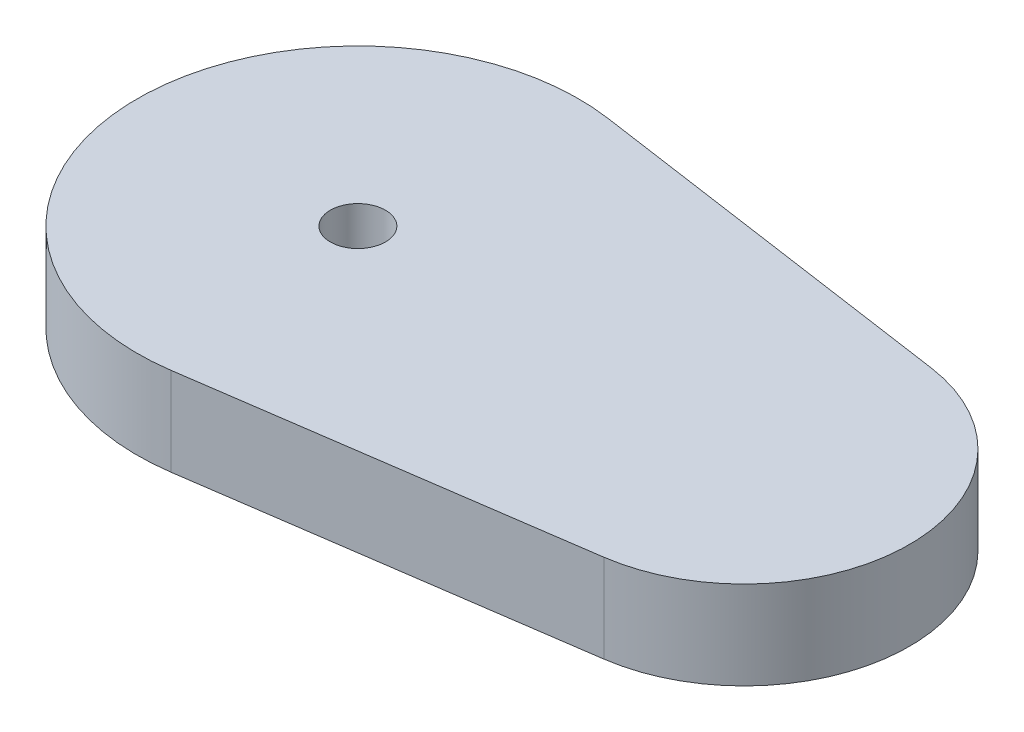
SolidWorks part; units mm, degrees
ref_plane "Front Plane" through (0, 0, 0) normal (0, 0, 1) x (1, 0, 0)
ref_plane "Top Plane" through (0, 0, 0) normal (0, 1, 0) x (1, 0, 0)
ref_plane "Right Plane" through (0, 0, 0) normal (1, 0, 0) x (0, 0, -1)
sketch "Sketch1" plane through (0, 0, 0) normal (0, 1, 0) x (1, 0, 0)
  line L0 (0, 0) -> (14, 0) construction
  line L6 (1.1429, -7.9179) -> (14.8571, -5.9385)
  line L8 (1.1429, 7.9179) -> (14.8571, 5.9385)
  line L11 (14, 0) -> (20, 0) construction
  circle A0 centre (0, 0) radius 1
  arc A1 (1.1429, 7.9179) -> (1.1429, -7.9179) centre (0, 0) ccw
  arc A2 (14.8571, 5.9385) -> (14.8571, -5.9385) centre (14, 0) cw
  point P3 (0, 0)
  dimension "D1" = 2
  dimension "D2" = 20
  dimension "D5" = 8
  dimension "D6" = 6
  dimension "D3" = 8
sketch "Sketch2" plane through (0, 0, 0) normal (0, 0, 1) x (1, 0, 0)
  line L0 (0, 0) -> (0, 3.2) construction
  point P4 (0, 0)
  dimension "D1" = 3.2
extrude "Boss-Extrude1" add sketch "Sketch1" along normal up to vertex (3.2 mm away) up to point (0, 3.2, 0)
equation "\"glass_width\" = 150"
equation "\"glass_height\"= 100"
equation "\"glass_thickness\"= 4"
equation "\"brood_space\"= 42"
equation "\"t1\"= 6"
equation "\"t2\"= 3.2"
equation "\"box_depth\"= \"brood_space\" + \"glass_thickness\" + \"glass_thickness\" + \"t2\" + \"t2\""
equation "\"box_width\"= \"glass_width\" + \"t1\" + \"t1\""
equation "\"food_height\"= 70"
equation "\"box_height\" = \"glass_height\" + ( \"t1\" * 3 ) + \"food_height\""
equation "\"D1@Sketch2\"=\"t2\""
